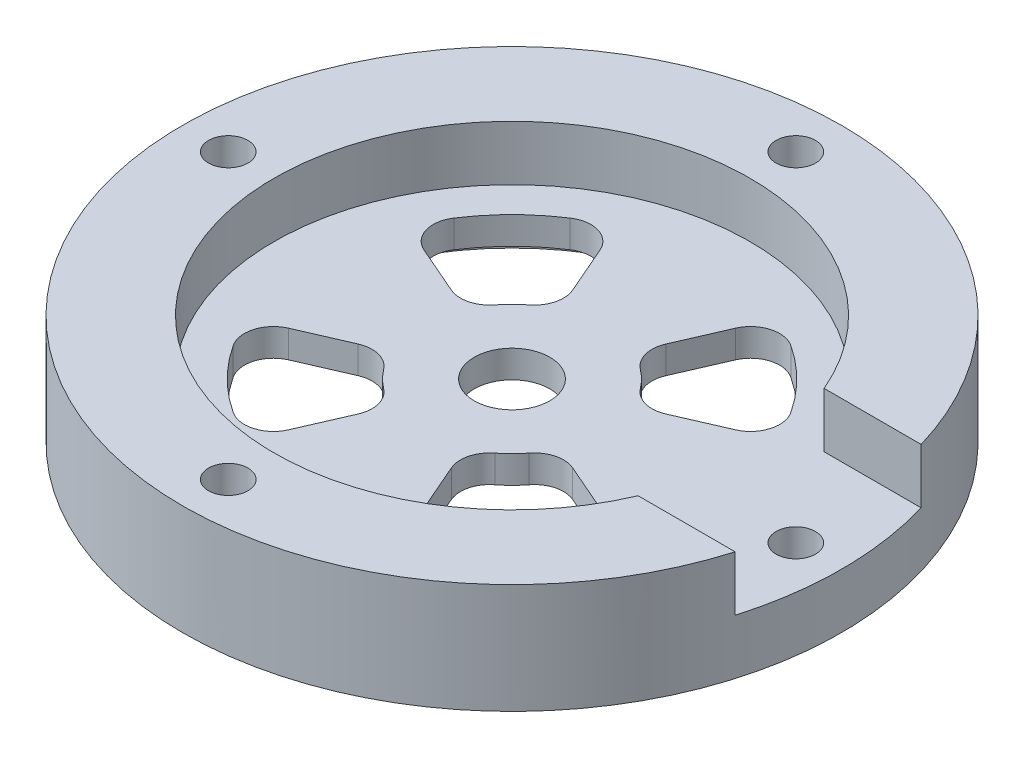
SolidWorks part; units mm, degrees
ref_plane "Front Plane" through (0, 0, 0) normal (0, 0, 1) x (1, 0, 0)
ref_plane "Top Plane" through (0, 0, 0) normal (0, 1, 0) x (1, 0, 0)
ref_plane "Right Plane" through (0, 0, 0) normal (1, 0, 0) x (0, 0, -1)
sketch "Sketch1" plane through (0, 0, 0) normal (0, 0, 1) x (1, 0, 0)
  line L0 (0, 0) -> (0, 12) construction
  line L1 (0, 3) -> (26, 3)
  line L2 (26, 3) -> (26, 0)
  line L3 (36, 12) -> (26, 12)
  line L4 (26, 12) -> (26, 6)
  line L5 (26, 6) -> (0, 6)
  line L6 (0, 6) -> (0, 3)
  line L7 (26, 0) -> (36, 0)
  line L8 (36, 0) -> (36, 12)
  dimension "D1" = 12
  dimension "D2" = 72
  dimension "D3" = 52
  dimension "D4" = 3
  dimension "D5" = 3
  dimension "D6" = 52
revolve "Revolve1" add sketch "Sketch1" angle 360 about L0
sketch "Sketch2" plane through (0, 6, 0) normal (0, 1, 0) x (1, 0, 0)
  line L0 (0, 0) -> (0, 26) construction
  line L1 (0, 0) -> (26, 0) construction
  line L2 (7.3989, 17.0163) -> (5.0987, 11.7262)
  line L3 (17.0163, 7.3989) -> (11.7262, 5.0987)
  line L4 (15.5563, 15.5563) -> (18.3848, 18.3848) construction
  line L5 (5.0987, 11.7262) -> (0, 11.7262) construction
  line L6 (11.7262, 5.0987) -> (11.7262, 0) construction
  line L7 (-7.3989, 17.0163) -> (-5.0987, 11.7262)
  line L8 (-17.0163, 7.3989) -> (-11.7262, 5.0987)
  line L9 (17.0163, -7.3989) -> (11.7262, -5.0987)
  line L10 (7.3989, -17.0163) -> (5.0987, -11.7262)
  line L11 (-7.3989, -17.0163) -> (-5.0987, -11.7262)
  line L12 (-17.0163, -7.3989) -> (-11.7262, -5.0987)
  circle A0 centre (0, 0) radius 26 construction
  arc A1 (12.0496, 18.4067) -> (18.4067, 12.0496) centre (0, 0) cw
  arc A2 (6.08, 7.9394) -> (7.9394, 6.08) centre (0, 0) cw
  arc A3 (7.9394, 6.08) -> (11.7262, 5.0987) centre (10.4602, 8.0104) ccw
  arc A4 (18.4067, 12.0496) -> (17.0163, 7.3989) centre (15.7503, 10.3106) cw
  arc A5 (12.0496, 18.4067) -> (7.3989, 17.0163) centre (10.3106, 15.7503) ccw
  arc A6 (6.08, 7.9394) -> (5.0987, 11.7262) centre (8.0104, 10.4602) cw
  arc A7 (-6.08, 7.9394) -> (-5.0987, 11.7262) centre (-8.0104, 10.4602) ccw
  arc A8 (-6.08, 7.9394) -> (-7.9394, 6.08) centre (0, 0) ccw
  arc A9 (-7.9394, 6.08) -> (-11.7262, 5.0987) centre (-10.4602, 8.0104) cw
  arc A10 (-18.4067, 12.0496) -> (-17.0163, 7.3989) centre (-15.7503, 10.3106) ccw
  arc A11 (-12.0496, 18.4067) -> (-18.4067, 12.0496) centre (0, 0) ccw
  arc A12 (-12.0496, 18.4067) -> (-7.3989, 17.0163) centre (-10.3106, 15.7503) cw
  arc A13 (6.08, -7.9394) -> (5.0987, -11.7262) centre (8.0104, -10.4602) ccw
  arc A14 (6.08, -7.9394) -> (7.9394, -6.08) centre (0, 0) ccw
  arc A15 (7.9394, -6.08) -> (11.7262, -5.0987) centre (10.4602, -8.0104) cw
  arc A16 (18.4067, -12.0496) -> (17.0163, -7.3989) centre (15.7503, -10.3106) ccw
  arc A17 (12.0496, -18.4067) -> (18.4067, -12.0496) centre (0, 0) ccw
  arc A18 (12.0496, -18.4067) -> (7.3989, -17.0163) centre (10.3106, -15.7503) cw
  arc A19 (-12.0496, -18.4067) -> (-7.3989, -17.0163) centre (-10.3106, -15.7503) ccw
  arc A20 (-6.08, -7.9394) -> (-5.0987, -11.7262) centre (-8.0104, -10.4602) cw
  arc A21 (-6.08, -7.9394) -> (-7.9394, -6.08) centre (0, 0) cw
  arc A22 (-7.9394, -6.08) -> (-11.7262, -5.0987) centre (-10.4602, -8.0104) ccw
  arc A23 (-12.0496, -18.4067) -> (-18.4067, -12.0496) centre (0, 0) cw
  arc A24 (-18.4067, -12.0496) -> (-17.0163, -7.3989) centre (-15.7503, -10.3106) cw
  dimension "D1" = 4
  dimension "D3" = 10
  dimension "D4" = 3.175
  dimension "D2" = 43
extrude "Cut-Extrude1" cut sketch "Sketch2" against normal up to next
hole_wizard "#18 (0.1695) Diameter Hole1" positions "Sketch4" profile "Sketch3" hole size "#18" standard "ANSI Inch"
sketch "Sketch4" plane through (0, 12, 0) normal (0, 1, 0) x (1, 0, 0)
  line L0 (0, 26) -> (0, 36) construction
  line L1 (0, 31) -> (0, -31) construction
  line L4 (-31, 0) -> (31, 0) construction
  circle A0 centre (0, 0) radius 26 construction
  circle A2 centre (0, 0) radius 36 construction
  point P10 (0, 31)
  point P28 (0, -31)
  point P33 (-31, 0)
  point P34 (31, 0)
sketch "Sketch3" plane through (0, 12, -31) normal (1, 0, 0) x (0, 0, 1)
  line L0 (0, 0) -> (0, 382.2934)
  line L1 (0, 382.2934) -> (2.1526, 381)
  line L2 (2.1526, 381) -> (2.1526, 0)
  line L5 (2.1526, 0) -> (0, 0)
  line L10 (0, 382.2934) -> (-2.1527, 381) construction
  line L11 (0, -6.35) -> (0, 107.95) construction
  dimension "Hole Dia." = 4.3053
  dimension "Hole Depth" = 381
  dimension "Drill Angle" = 118
sketch "Sketch5" plane through (0, 6, 0) normal (0, 1, 0) x (1, 0, 0)
  circle A0 centre (0, 0) radius 4.1275
  dimension "D1" = 8.255
extrude "Cut-Extrude2" cut sketch "Sketch5" against normal up to next
sketch "Sketch6" plane through (0, 0, 0) normal (0, -1, 0) x (1, 0, 0)
  line L1 (22.012, 10.16) -> (37.5295, 10.16)
  line L2 (22.012, 10.16) -> (22.012, -10.16)
  line L3 (22.012, -10.16) -> (37.5295, -10.16)
  line L4 (37.5295, 10.16) -> (37.5295, -10.16)
  line L5 (22.012, 10.16) -> (37.5295, -10.16) construction
  line L6 (22.012, -10.16) -> (37.5295, 10.16) construction
  point P0 (29.7707, 0)
  dimension "D1" = 20.32
extrude "Cut-Extrude5" cut sketch "Sketch6" against normal up to surface (12 mm away) from offset 6 up to face at (0, 12, -28.8474) offset against normal yes
